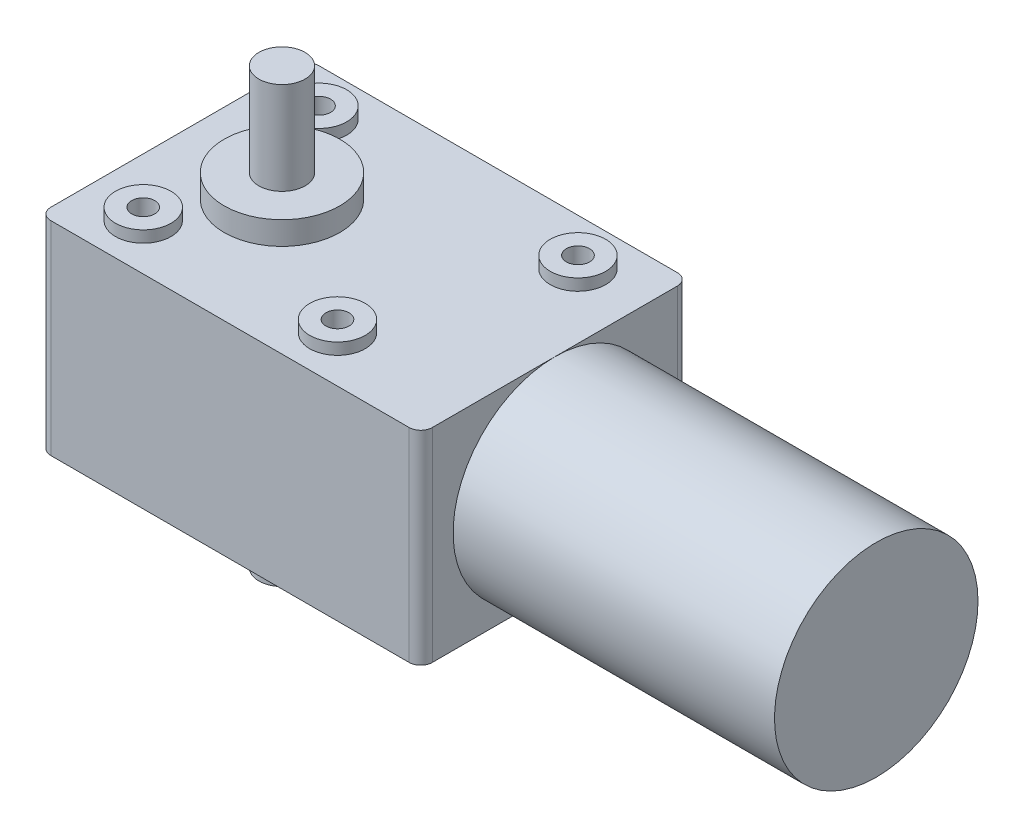
SolidWorks part; units mm, degrees
ref_plane "Front Plane" through (0, 0, 0) normal (0, 0, 1) x (1, 0, 0)
ref_plane "Top Plane" through (0, 0, 0) normal (0, 1, 0) x (1, 0, 0)
ref_plane "Right Plane" through (0, 0, 0) normal (1, 0, 0) x (0, 0, -1)
sketch "Sketch1" plane through (0, 0, 0) normal (0, 1, 0) x (1, 0, 0)
  line L1 (-38.75, -29) -> (38.75, -29)
  line L2 (-41.25, -26.5) -> (-41.25, 26.5)
  line L3 (-38.75, 29) -> (38.75, 29)
  line L4 (41.25, -26.5) -> (41.25, 26.5)
  line L5 (-41.25, -29) -> (41.25, 29) construction
  line L6 (-41.25, 29) -> (41.25, -29) construction
  arc A0 (-41.25, -26.5) -> (-38.75, -29) centre (-38.75, -26.5) ccw
  arc A1 (38.75, -29) -> (41.25, -26.5) centre (38.75, -26.5) ccw
  arc A2 (41.25, 26.5) -> (38.75, 29) centre (38.75, 26.5) ccw
  arc A3 (-41.25, 26.5) -> (-38.75, 29) centre (-38.75, 26.5) cw
  point P0 (0, 0)
  dimension "D3" = 2.5
  dimension "D1" = 82.5
  dimension "D2" = 58
extrude "Boss-Extrude1" add sketch "Sketch1" along normal mid plane 44
sketch "Sketch2" plane through (0, 22, 0) normal (0, 1, 0) x (1, 0, 0)
  line L0 (-1000, 0) -> (49000, 0) construction
  line L1 (-1000.4558, 19) -> (48999.5442, 19) construction
  line L2 (-1000.9116, -19) -> (48999.0884, -19) construction
  line L3 (-28.75, -994.0746) -> (-28.75, 49005.9254) construction
  line L4 (27.25, -995.2141) -> (27.25, 49004.7859) construction
  line L5 (-41.25, 26.5) -> (-41.25, -26.5) construction
  line L6 (13.25, -1014) -> (13.25, 48986) construction
  circle A0 centre (-28.75, 19) radius 6
  circle A1 centre (-28.75, -19) radius 6
  circle A2 centre (13.25, -19) radius 6
  circle A3 centre (27.25, 19) radius 6
  dimension "D5" = 12
  dimension "D6" = 12
  dimension "D7" = 12
  dimension "D8" = 12
  dimension "D9" = 42
  dimension "D1" = 19
  dimension "D2" = 19
  dimension "D3" = 12.5
  dimension "D4" = 56
extrude "Boss-Extrude2" add sketch "Sketch2" along normal blind 2.5
sketch "Sketch3" plane through (0, 24.5, 0) normal (0, 1, 0) x (1, 0, 0)
  circle A0 centre (-28.75, 19) radius 2.5
  circle A1 centre (27.25, 19) radius 2.5
  circle A2 centre (13.25, -19) radius 2.5
  circle A3 centre (-28.75, -19) radius 2.5
  dimension "D1" = 5
  dimension "D2" = 5
  dimension "D3" = 5
  dimension "D4" = 5
extrude "Cut-Extrude1" cut sketch "Sketch3" against normal blind 6
sketch "Sketch6" plane through (0, 22, 0) normal (0, 1, 0) x (1, 0, 0)
  line L0 (-1000, 0) -> (49000, 0) construction
  line L1 (-41.25, 26.5) -> (-41.25, -26.5) construction
  circle A0 centre (-17.75, 0) radius 12.5
  dimension "D1" = 25
  dimension "D2" = 23.5
extrude "Boss-Extrude5" add sketch "Sketch6" along normal blind 5
sketch "Sketch4" plane through (0, 27, 0) normal (0, 1, 0) x (1, 0, 0)
  circle A0 centre (-17.75, 0) radius 5
  circle A1 centre (-17.75, 0) radius 12.5 construction
  dimension "D1" = 10
extrude "Boss-Extrude3" add sketch "Sketch4" along normal blind 20
sketch "Sketch5" plane through (41.25, 0, 0) normal (1, 0, 0) x (0, 0, -1)
  line L1 (0, -1000) -> (0, 49000) construction
  circle A0 centre (0, 0) radius 22
  dimension "D2" = 44
extrude "Boss-Extrude4" add sketch "Sketch5" along normal blind 69.5
mirror "Mirror2" about plane through (0, 0, 0) normal (0, 1, 0) of "Boss-Extrude3", "Boss-Extrude2", "Cut-Extrude1", "Boss-Extrude5"
